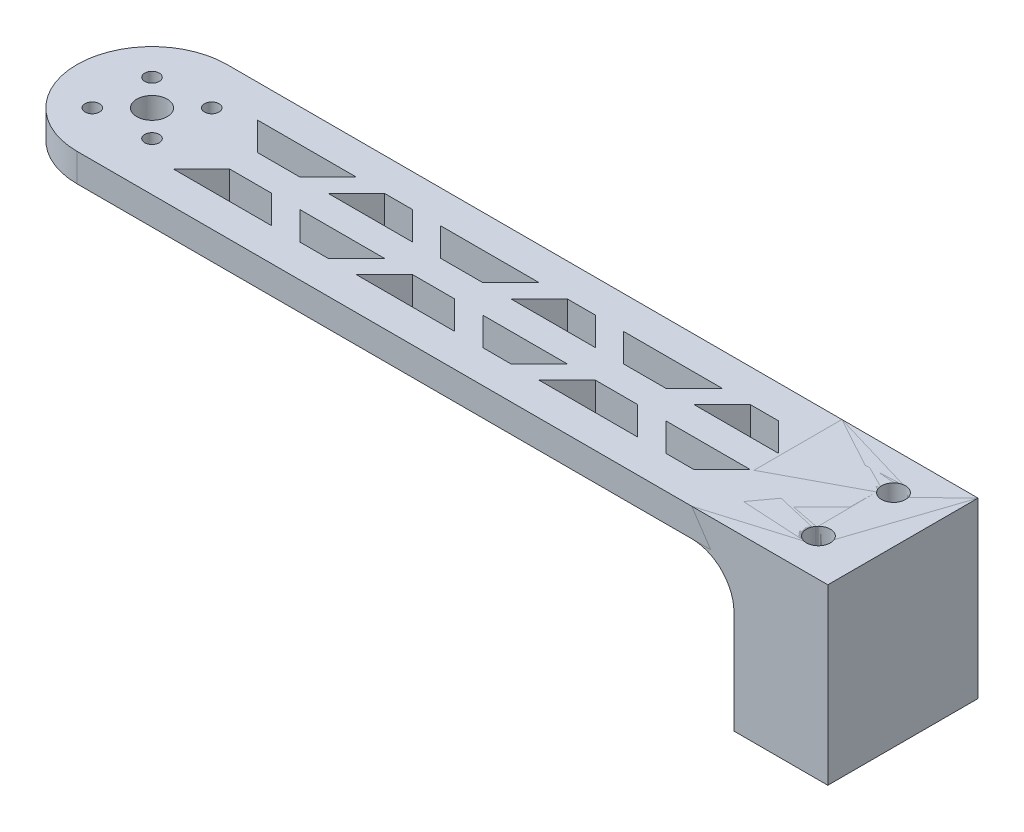
SolidWorks part; units mm, degrees
material "Custom Plastic"
ref_plane "Front Plane" through (0, 0, 0) normal (0, 0, 1) x (1, 0, 0)
ref_plane "Top Plane" through (0, 0, 0) normal (0, 1, 0) x (1, 0, 0)
ref_plane "Right Plane" through (0, 0, 0) normal (1, 0, 0) x (0, 0, -1)
sketch "Sketch1" plane through (0, 0, 0) normal (0, 1, 0) x (1, 0, 0)
  line L0 (0, -16) -> (160, -16)
  line L1 (0, 16) -> (160, 16)
  line L3 (160, 16) -> (160, -16)
  arc A0 (0, 16) -> (0, -16) centre (0, 0) ccw
  dimension "D2" = 16
  dimension "D3" = 32
  dimension "D4" = 160
  dimension "D1" = 160
extrude "Boss-Extrude1" add sketch "Sketch1" against normal blind 6
sketch "Sketch11" plane through (0, 0, 0) normal (0, 1, 0) x (1, 0, 0)
  line L0 (0, 0) -> (160, 0) construction
  line L1 (160, -16) -> (160, 16) construction
  line L2 (13.5, 9) -> (19.5, 3)
  line L3 (19.5, 3) -> (28.5, 3)
  line L4 (28.5, 3) -> (34.5, 9)
  line L5 (34.5, 9) -> (13.5, 9)
  line L6 (52.5, 3) -> (46.5, 9)
  line L7 (46.5, 9) -> (40.5, 9)
  line L8 (40.5, 9) -> (34.5, 3)
  line L9 (34.5, 3) -> (52.5, 3)
  line L10 (24, 9) -> (24, 3) construction
  line L11 (52.5, 9) -> (58.5, 3)
  line L12 (73.5, 9) -> (52.5, 9)
  line L13 (67.5, 3) -> (73.5, 9)
  line L14 (58.5, 3) -> (67.5, 3)
  line L15 (91.5, 9) -> (97.5, 3)
  line L16 (112.5, 9) -> (91.5, 9)
  line L17 (106.5, 3) -> (112.5, 9)
  line L18 (97.5, 3) -> (106.5, 3)
  line L24 (73.5, 3) -> (91.5, 3)
  line L25 (145.5, 3) -> (151.5, 9) [skipped]
  line L26 (79.5, 9) -> (73.5, 3)
  line L27 (85.5, 9) -> (79.5, 9)
  line L28 (91.5, 3) -> (85.5, 9)
  line L29 (112.5, 3) -> (130.5, 3)
  line L30 (118.5, 9) -> (112.5, 3)
  line L31 (124.5, 9) -> (118.5, 9)
  line L32 (130.5, 3) -> (124.5, 9)
  line L33 (130.5, 9) -> (136.5, 3) [skipped]
  line L34 (139.5, 9) -> (130.5, 9) [skipped]
  line L35 (136.5, 3) -> (139.5, 3) [skipped]
  point P15 (24, 3)
  dimension "D1" = 6
  dimension "D2" = 21
  dimension "D3" = 45
  dimension "D4" = 45
  dimension "D5" = 24
  dimension "D6" = 3
  dimension "D7" = 45
  dimension "D8" = 45
  dimension "D9" = 6
  dimension "D10" = 18
  dimension "D11" = 3
  dimension "D12" = 6
  dimension "D13" = 4
  dimension "D14" = 6
  dimension "D16" = 6
  dimension "D15" = 3
extrude "Cut-Extrude3" cut sketch "Sketch11" against normal up to next
mirror "Mirror1" about plane through (0, 0, 0) normal (0, 0, 1) of "Cut-Extrude3"
sketch "Sketch14" plane through (0, 0, 0) normal (0, 0, 1) x (1, 0, 0)
  line L0 (160, -6) -> (160, -37)
  line L1 (160, -37) -> (140, -37)
  line L5 (140, -37) -> (140, -15)
  line L6 (0, -6) -> (160, -6) construction
  line L8 (131, -6) -> (131, 0)
  line L9 (0, 0) -> (160, 0) construction
  line L10 (131, 0) -> (160, 0)
  line L11 (160, 0) -> (160, -6)
  arc A0 (140, -15) -> (131, -6) centre (131, -15) ccw
  dimension "D4" = 9
  dimension "D1" = 31
  dimension "D2" = 20
  dimension "D3" = 22
extrude "Boss-Extrude12" add sketch "Sketch14" along normal mid plane 32 separate body
sketch "Sketch8" plane through (0, 0, 0) normal (0, 1, 0) x (1, 0, 0)
  line L0 (160, -16) -> (160, 16) construction
  line L1 (160, 16) -> (0, 16) construction
  line L2 (0, -16) -> (160, -16) construction
  circle A0 centre (150, 8) radius 2.55
  circle A1 centre (150, -8) radius 2.55
  dimension "D1" = 5.1
  dimension "D2" = 10
  dimension "D4" = 8
  dimension "D5" = 16
  dimension "D6" = 10
  dimension "D3" = 8
extrude "Cut-Extrude4" cut sketch "Sketch8" against normal through all
ref_plane "Plane1" through (0, -37, 0) normal (0, -1, 0) x (-1, 0, 0)
sketch "Sketch16" plane through (0, -37, 0) normal (0, -1, 0) x (-1, 0, 0)
  line L0 (-160, 16) -> (-160, 36)
  line L1 (-160, 36) -> (-140, 16)
  line L2 (-160, 16) -> (-140, 16)
  line L3 (-3.3, 0) -> (3.3, 0) construction
  line L4 (-160, -16) -> (-140, -16)
  line L5 (-160, -36) -> (-140, -16)
  line L6 (-160, -16) -> (-160, -36)
  dimension "D1" = 20
sketch "Sketch10" plane through (0, 0, 0) normal (0, 1, 0) x (1, 0, 0)
  line L0 (-9.0001, 0) -> (9.0001, 0) construction
  line L1 (0, 0) -> (6.3641, 6.3641) construction
  line L2 (-5.6569, 5.6569) -> (0, 0) construction
  line L3 (-6.3641, -6.3641) -> (0, 0) construction
  line L4 (0, 0) -> (5.6569, -5.6569) construction
  circle A0 centre (0, 0) radius 9.0001 construction
  circle A1 centre (0, 0) radius 8 construction
  circle A2 centre (-6.3641, -6.3641) radius 1.55
  circle A3 centre (6.3641, 6.3641) radius 1.55
  circle A4 centre (5.6569, -5.6569) radius 1.55
  circle A5 centre (-5.6569, 5.6569) radius 1.55
  circle A6 centre (0, 0) radius 3.25
  dimension "D1" = 18.0003
  dimension "D2" = 16
  dimension "D3" = 3.1
  dimension "D8" = 6.5
  dimension "D4" = 45
  dimension "D5" = 45
  dimension "D6" = 45
  dimension "D7" = 45
extrude "Cut-Extrude2" cut sketch "Sketch10" against normal up to next (6 mm away)
sketch "Sketch17" plane through (0, 0, 0) normal (0, 1, 0) x (1, 0, 0)
  arc A0 (-1.4069, 5.6569) -> (-5.6569, 1.4069) centre (-5.6569, 5.6569) ccw
  arc A1 (-6.3641, -2.1141) -> (-2.1141, -6.3641) centre (-6.3641, -6.3641) ccw
  arc A2 (1.4661, -6.3641) -> (5.6569, -1.4069) centre (5.6569, -5.6569) ccw
  arc A3 (6.3641, 2.1141) -> (2.1733, 5.6569) centre (6.3641, 6.3641) ccw
  arc A4 (-5.6569, 1.4069) -> (-6.3641, -2.1141) centre (-10.5855, 0.5653) cw
  arc A5 (-2.1141, -6.3641) -> (1.4661, -6.3641) centre (-0.324, -11.0326) cw
  arc A6 (-1.4069, 5.6569) -> (2.1733, 5.6569) centre (0.3832, 10.3254) ccw
  arc A7 (6.3641, 2.1141) -> (5.6569, -1.4069) centre (10.5855, -0.5653) ccw
  circle A8 centre (-6.3641, -6.3641) radius 1.525
  circle A10 centre (-5.6569, 5.6569) radius 1.525
  circle A11 centre (6.3641, 6.3641) radius 1.525
  circle A12 centre (5.6569, -5.6569) radius 1.525
  circle A13 centre (0, 0) radius 3.25
  dimension "D1" = 8.5
  dimension "D2" = 5
  dimension "D3" = 3.05
  dimension "D4" = 6.5
equation "\"arm-width\"= 32"
equation "\"D2@Sketch1\"=\"arm-width\"/2"
equation "\"arm-length\"= 160"
equation "\"D3@Sketch1\"=\"arm-width\""
equation "\"D4@Sketch1\"= \"arm-length\""
equation "\"D1@Boss-Extrude12\"=\"arm-width\""
